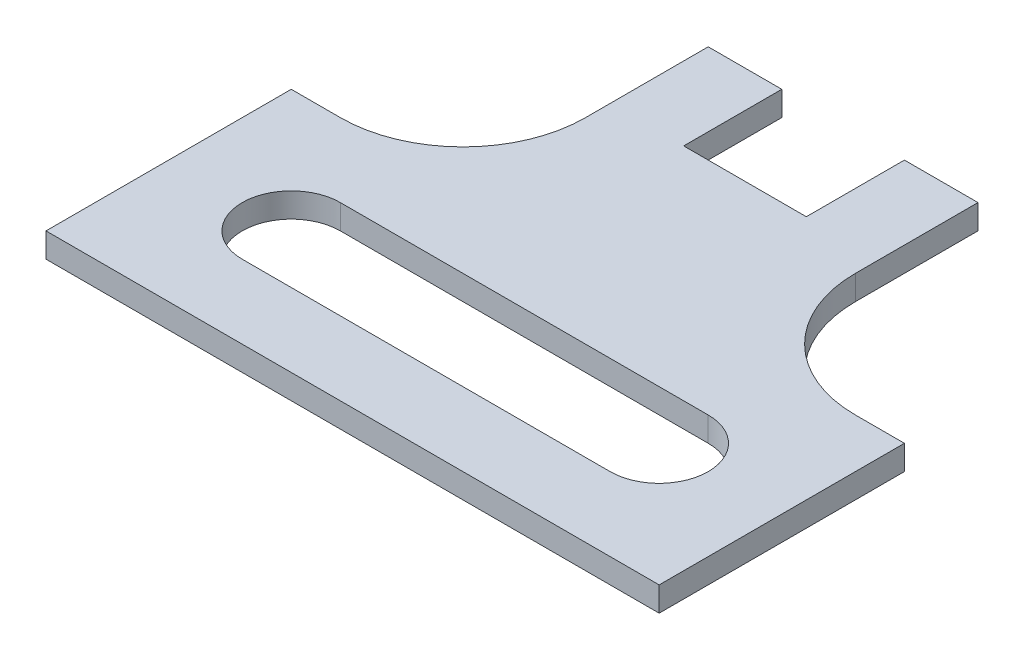
SolidWorks part; units mm, degrees
ref_plane "Front Plane" through (0, 0, 0) normal (0, 0, 1) x (1, 0, 0)
ref_plane "Top Plane" through (0, 0, 0) normal (0, 1, 0) x (1, 0, 0)
ref_plane "Right Plane" through (0, 0, 0) normal (1, 0, 0) x (0, 0, -1)
sketch "Sketch1" plane through (0, 0, 0) normal (0, 1, 0) x (1, 0, 0)
  line L0 (5, 5) -> (20, 5) construction
  line L1 (0, 0) -> (25, 0)
  line L2 (0, 0) -> (0, 10)
  line L3 (0, 10) -> (2, 10)
  line L4 (25, 0) -> (25, 10)
  line L6 (7, 15) -> (7, 20)
  line L7 (7, 20) -> (10, 20)
  line L8 (18, 15) -> (18, 20)
  line L10 (10, 20) -> (10, 16)
  line L11 (10, 16) -> (15, 16)
  line L12 (15, 20) -> (15, 16)
  line L13 (5, 7) -> (20, 7)
  line L14 (5, 3) -> (20, 3)
  line L15 (23, 10) -> (25, 10)
  line L16 (15, 20) -> (18, 20)
  arc A0 (5, 7) -> (5, 3) centre (5, 5) ccw
  arc A1 (20, 3) -> (20, 7) centre (20, 5) ccw
  arc A2 (7, 15) -> (2, 10) centre (2, 15) cw
  arc A3 (23, 10) -> (18, 15) centre (23, 15) cw
  point P15 (12.5, 5)
  dimension "D5" = 4
  dimension "D6" = 5
  dimension "D7" = 5
  dimension "D1" = 25
  dimension "D2" = 5
  dimension "D3" = 20
  dimension "D4" = 5
  dimension "D8" = 15
  dimension "D9" = 2
  dimension "D10" = 2
  dimension "D11" = 20
  dimension "D12" = 4
  dimension "D13" = 10
  dimension "D14" = 15
extrude "Boss-Extrude1" add sketch "Sketch1" along normal blind 1
ref_axis "Axis1" through (3, 1, -5) along (1, 0, 0)
